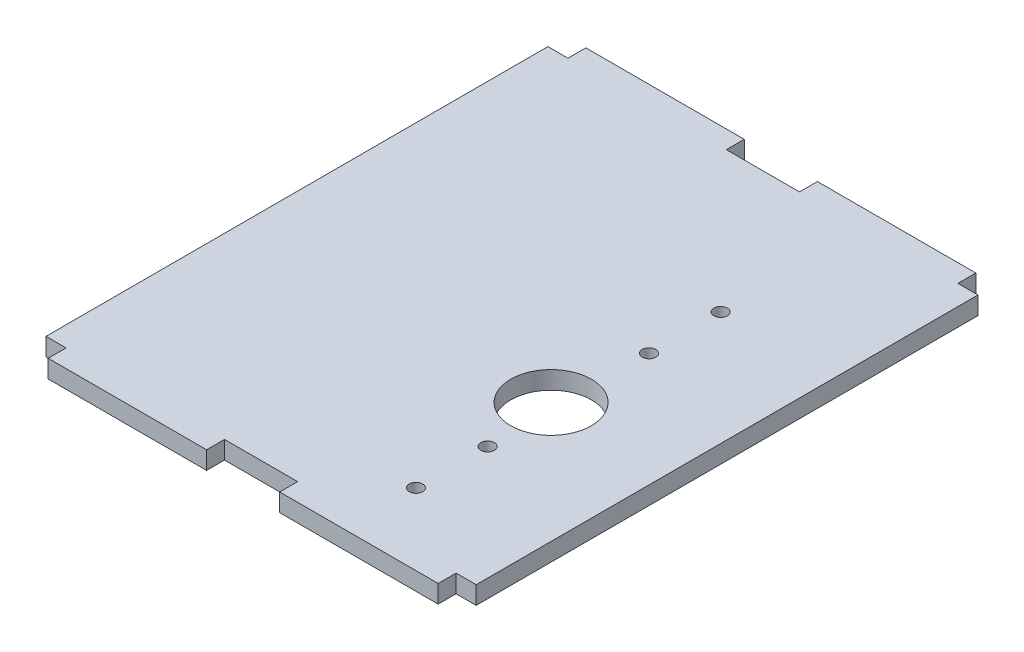
SolidWorks part; units mm, degrees
ref_plane "Front Plane" through (0, 0, 0) normal (0, 0, 1) x (1, 0, 0)
ref_plane "Top Plane" through (0, 0, 0) normal (0, 1, 0) x (1, 0, 0)
ref_plane "Right Plane" through (0, 0, 0) normal (1, 0, 0) x (0, 0, -1)
sketch "Sketch1" plane through (0, 0, 0) normal (0, 1, 0) x (1, 0, 0)
  line L1 (0, 0) -> (304.8, 0)
  line L2 (0, 0) -> (0, 355.6)
  line L3 (0, 355.6) -> (304.8, 355.6)
  line L4 (304.8, 0) -> (304.8, 355.6)
  ellipse E0 centre (219.5122, 138.3861) end of major axis (248.0872, 138.3861) minor radius 28.574 construction
  ellipse E1 centre (219.5122, 138.3861) end of major axis (248.0872, 138.3861) minor radius 28.574
  dimension "D1" = 355.6
  dimension "D2" = 304.8
extrude "Boss-Extrude1" add sketch "Sketch1" along normal blind 12.7
sketch "Sketch2" plane through (0, 0, 0) normal (0, -1, 0) x (1, 0, 0)
  line L0 (0, 0) -> (304.8, 0) construction
  line L1 (0, -355.6) -> (0, 0) construction
  circle A0 centre (224.028, -38.1) radius 4.7625
  circle A1 centre (224.028, -88.9) radius 4.7625
  circle A2 centre (224.028, -203.2) radius 4.7625
  circle A3 centre (224.028, -254) radius 4.7625
  dimension "D3" = 88.9
  dimension "D6" = 9.525
  dimension "D1" = 38.1
  dimension "D2" = 224.028
  dimension "D4" = 203.2
  dimension "D5" = 254
  dimension "D7" = 224.028
  dimension "D8" = 224.028
  dimension "D9" = 224.028
extrude "Cut-Extrude1" cut sketch "Sketch2" against normal blind 12.7
sketch "Sketch3" plane through (0, 12.7, 0) normal (0, 1, 0) x (1, 0, 0)
  line L0 (152.4, 355.6) -> (152.4, 250.206) construction
  line L1 (0, 177.8) -> (22.2548, 177.8) construction
  line L2 (14.224, 355.6) -> (126.492, 355.6)
  line L3 (14.224, 355.6) -> (14.224, 368.3)
  line L4 (0, 355.6) -> (0, 0)
  line L5 (0, 0) -> (304.8, 0)
  line L6 (304.8, 0) -> (304.8, 355.6)
  line L7 (304.8, 355.6) -> (0, 355.6)
  line L8 (0, 355.6) -> (0, 0) construction
  line L9 (0, 0) -> (304.8, 0) construction
  line L10 (304.8, 0) -> (304.8, 355.6) construction
  line L11 (304.8, 355.6) -> (0, 355.6) construction
  line L12 (14.224, 368.3) -> (126.492, 368.3)
  line L13 (126.492, 355.6) -> (126.492, 368.3)
  line L14 (290.576, 368.3) -> (178.308, 368.3)
  line L15 (178.308, 355.6) -> (178.308, 368.3)
  line L16 (290.576, 355.6) -> (178.308, 355.6)
  line L17 (290.576, 355.6) -> (290.576, 368.3)
  line L18 (290.576, 0) -> (290.576, -12.7)
  line L19 (290.576, 0) -> (178.308, 0)
  line L20 (178.308, 0) -> (178.308, -12.7)
  line L21 (290.576, -12.7) -> (178.308, -12.7)
  line L22 (14.224, -12.7) -> (126.492, -12.7)
  line L23 (126.492, 0) -> (126.492, -12.7)
  line L24 (14.224, 0) -> (126.492, 0)
  line L25 (14.224, 0) -> (14.224, -12.7)
  dimension "D2" = 25.908
  dimension "D3" = 112.268
  dimension "D4" = 12.7
  dimension "D1" = 0
extrude "Boss-Extrude2" add sketch "Sketch3" against normal blind 12.7
sketch "Sketch4" plane through (0, 0, 0) normal (0, -1, 0) x (1, 0, 0)
  line L20 (0, 0) -> (0, -355.6)
  line L21 (0, -355.6) -> (14.224, -355.6)
  line L22 (14.224, -355.6) -> (14.224, -368.3)
  line L23 (14.224, -368.3) -> (126.492, -368.3)
  line L24 (126.492, -368.3) -> (126.492, -355.6)
  line L25 (126.492, -355.6) -> (178.308, -355.6)
  line L26 (178.308, -355.6) -> (178.308, -368.3)
  line L27 (178.308, -368.3) -> (290.576, -368.3)
  line L28 (290.576, -368.3) -> (290.576, -355.6)
  line L29 (290.576, -355.6) -> (304.8, -355.6)
  line L30 (304.8, -355.6) -> (304.8, 0)
  line L31 (304.8, 0) -> (290.576, 0)
  line L32 (290.576, 0) -> (290.576, 12.7)
  line L33 (290.576, 12.7) -> (178.308, 12.7)
  line L34 (178.308, 12.7) -> (178.308, 0)
  line L35 (178.308, 0) -> (126.492, 0)
  line L36 (126.492, 0) -> (126.492, 12.7)
  line L37 (126.492, 12.7) -> (14.224, 12.7)
  line L38 (14.224, 12.7) -> (14.224, 0)
  line L39 (14.224, 0) -> (0, 0)
  line L40 (0, 0) -> (0, -355.6)
  line L41 (0, -355.6) -> (14.224, -355.6)
  line L42 (14.224, -355.6) -> (14.224, -368.3)
  line L43 (14.224, -368.3) -> (126.492, -368.3)
  line L44 (126.492, -368.3) -> (126.492, -355.6)
  line L45 (126.492, -355.6) -> (178.308, -355.6)
  line L46 (178.308, -355.6) -> (178.308, -368.3)
  line L47 (178.308, -368.3) -> (290.576, -368.3)
  line L48 (290.576, -368.3) -> (290.576, -355.6)
  line L49 (290.576, -355.6) -> (304.8, -355.6)
  line L50 (304.8, -355.6) -> (304.8, 0)
  line L51 (304.8, 0) -> (290.576, 0)
  line L52 (290.576, 0) -> (290.576, 12.7)
  line L53 (290.576, 12.7) -> (178.308, 12.7)
  line L54 (178.308, 12.7) -> (178.308, 0)
  line L55 (178.308, 0) -> (126.492, 0)
  line L56 (126.492, 0) -> (126.492, 12.7)
  line L57 (126.492, 12.7) -> (14.224, 12.7)
  line L58 (14.224, 12.7) -> (14.224, 0)
  line L59 (14.224, 0) -> (0, 0)
  circle A5 centre (224.028, -203.2) radius 4.7625 construction
  circle A6 centre (224.028, -88.9) radius 4.7625 construction
  dimension "D3" = 109.5375
  dimension "D1" = 0
